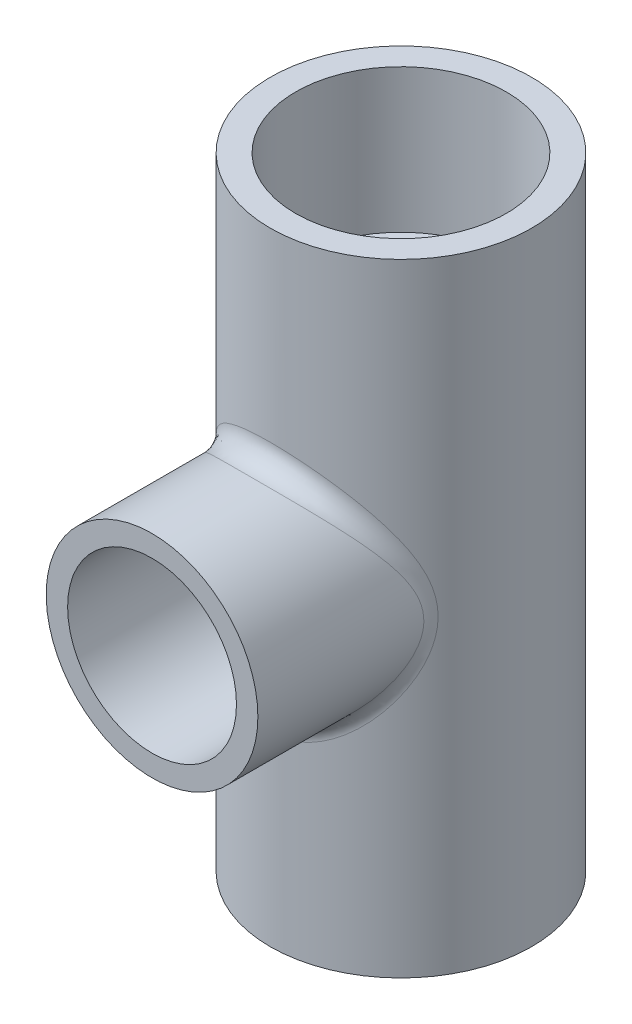
SolidWorks part; units mm, degrees
ref_plane "Front Plane" through (0, 0, 0) normal (0, 0, 1) x (1, 0, 0)
ref_plane "Top Plane" through (0, 0, 0) normal (0, 1, 0) x (1, 0, 0)
ref_plane "Right Plane" through (0, 0, 0) normal (1, 0, 0) x (0, 0, -1)
sketch "Sketch1" plane through (0, 0, 0) normal (0, 1, 0) x (1, 0, 0)
  circle A0 centre (0, 0) radius 656.5
  circle A1 centre (0, 0) radius 412
  dimension "D1" = 1313
  dimension "D2" = 824
extrude "Boss-Extrude1" add sketch "Sketch1" along normal blind 3125
sketch "Sketch2" plane through (0, 3125, 0) normal (0, 1, 0) x (1, 0, 0)
  circle A0 centre (0, 0) radius 529
  dimension "D1" = 1058
extrude "Cut-Extrude1" cut sketch "Sketch2" against normal blind 720
sketch "Sketch3" plane through (0, 0, 0) normal (0, -1, 0) x (1, 0, 0)
  circle A0 centre (0, 0) radius 529
  dimension "D1" = 1058
extrude "Cut-Extrude2" cut sketch "Sketch3" against normal blind 720
sketch "Sketch4" plane through (0, 0, 0) normal (0, 0, 1) x (1, 0, 0)
  line L0 (0, 0) -> (0, 3125) construction
  line L1 (529, 3125) -> (-529, 3125) construction
  line L2 (-656.5, 1562.5) -> (656.5, 1562.5) construction
  line L3 (-656.5, 3125) -> (-656.5, 0) construction
  line L4 (656.5, 0) -> (656.5, 3125) construction
  circle A0 centre (0, 1562.5) radius 311
  circle A1 centre (0, 1562.5) radius 531.5
  dimension "D1" = 622
  dimension "D2" = 1063
extrude "Boss-Extrude2" add sketch "Sketch4" along normal blind 1250
sketch "Sketch5" plane through (0, 0, 1250) normal (0, 0, 1) x (1, 0, 0)
  circle A0 centre (0, 1562.5) radius 424
  dimension "D1" = 848
extrude "Cut-Extrude3" cut sketch "Sketch5" against normal blind 690
sketch "Sketch6" plane through (0, 0, 560) normal (0, 0, 1) x (1, 0, 0)
  circle A0 centre (0, 1562.5) radius 311
  dimension "D1" = 622
extrude "Cut-Extrude4" cut sketch "Sketch6" against normal blind 690
sketch "Sketch7" plane through (0, 0, 0) normal (0, -1, 0) x (1, 0, 0)
  circle A0 centre (0, 0) radius 412
extrude "Cut-Extrude5" cut sketch "Sketch7" against normal through all
fillet "Fillet1" radius 100 1 edges at (524.4649, 1648.6906, 394.8782)
